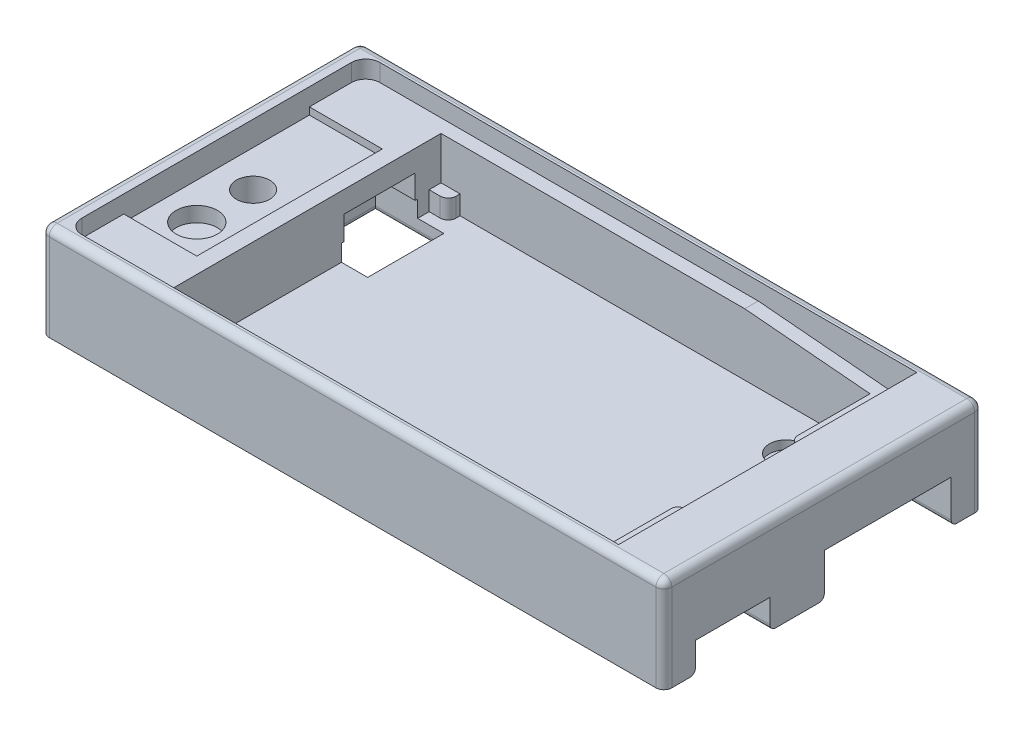
SolidWorks part; units mm, degrees
ref_plane "前视基准面" through (0, 0, 0) normal (0, 0, 1) x (1, 0, 0)
ref_plane "上视基准面" through (0, 0, 0) normal (0, 1, 0) x (1, 0, 0)
ref_plane "右视基准面" through (0, 0, 0) normal (1, 0, 0) x (0, 0, -1)
other "Configuration Table"
sketch "草图1" plane through (0, 0, 0) normal (0, 1, 0) x (1, 0, 0)
  line L0 (-39.25, 0) -> (39.25, 0) construction
  line L1 (-39.25, 20.1) -> (39.25, 20.1)
  line L2 (-39.25, 20.1) -> (-39.25, -20.1)
  line L3 (-39.25, -20.1) -> (39.25, -20.1)
  line L4 (39.25, 20.1) -> (39.25, -20.1)
  line L5 (-39.25, 20.1) -> (39.25, -20.1) construction
  line L6 (-39.25, -20.1) -> (39.25, 20.1) construction
  line L7 (-26.05, -17.1) -> (28.05, -17.1)
  line L8 (-26.05, -17.1) -> (-26.05, 17.1)
  line L9 (-26.05, 17.1) -> (28.05, 17.1)
  line L10 (28.05, -17.1) -> (28.05, 17.1)
  line L12 (32.25, 6.9973) -> (34.45, 6.9973)
  line L13 (32.25, 6.9973) -> (32.25, -6.9973)
  line L14 (32.25, -6.9973) -> (34.45, -6.9973)
  line L15 (34.45, 6.9973) -> (34.45, -6.9973)
  line L16 (-37.25, 18.8) -> (32.25, 18.8)
  line L17 (-37.25, 18.8) -> (-37.25, -18.8)
  line L18 (-37.25, -18.8) -> (32.25, -18.8)
  line L19 (32.25, 18.8) -> (32.25, -18.8)
  circle A0 centre (-32.65, 7.1) radius 2.6
  circle A1 centre (-32.65, 0) radius 2.1
  circle A2 centre (22.85, 11.6973) radius 2.1
  circle A3 centre (22.85, -11.6973) radius 2.1
  circle A4 centre (-32.65, -7.1) radius 2.6
  point P0 (0, 0)
  dimension "D1" = 4.2
  dimension "D6" = 5.2
  dimension "D2" = 5.2
  dimension "D3" = 5.4027
  dimension "D4" = 6.6
  dimension "D5" = 13
  dimension "D7" = 3
  dimension "D8" = 3
  dimension "D9" = 6.6
  dimension "D10" = 11.2
  dimension "D11" = 54.1
  dimension "D12" = 34.2
  dimension "D13" = 2.2
  dimension "D14" = 4.7
  dimension "D15" = 1.3
  dimension "D16" = 1.3
  dimension "D17" = 2
  dimension "D18" = 7
extrude "凸台-拉伸2" add sketch "草图1" along normal blind 2.2 contours L4 L1 L2 L3 L16 L19 L10 L12 L15 L14 L18 L17 | L15 L12 L10 L14 region at (0, 0, -19.2181) region at (33.35, 0, 0)
extrude "凸台-拉伸3" add sketch "草图1<4>" against normal blind 7.8 contours L19 L16 L17 L18 L7 L8 L9 A0 A1 A4 | L4 L1 L2 L3 L16 L19 L10 L12 L15 L14 L18 L17 | A4 | A0 | A1 | L15 L12 L13 L14 region at (0, 0, -19.2181) region at (33.35, 0, 0) region at (31.4598, 0, 0) region at (-32.65, 0, -7.1) region at (-32.65, 0, 0) region at (-32.65, 0, 7.1)
sketch "草图1<4>" plane through (0, 0, 0) normal (0, 1, 0) x (1, 0, 0) same geometry as "草图1"
sketch "草图2" plane through (0, 0, 0) normal (0, 1, 0) x (1, 0, 0)
  line L0 (-37.25, 18.8) -> (-37.25, -18.8) construction
  line L1 (-37.25, 11.7) -> (-28.05, 11.7)
  line L2 (-37.25, 11.7) -> (-37.25, -11.7)
  line L3 (-37.25, -11.7) -> (-28.05, -11.7)
  line L4 (-28.05, 11.7) -> (-28.05, -11.7)
  circle A0 centre (-32.65, 7.1) radius 2.6 construction
  circle A1 centre (-32.65, 7.1) radius 2.6 construction
  circle A2 centre (-32.65, -7.1) radius 2.6 construction
  circle A3 centre (-32.65, -7.1) radius 2.6 construction
  dimension "D1" = 4.6
  dimension "D2" = 4.6
  dimension "D3" = 4.6
extrude "切除-拉伸1" cut sketch "草图2" against normal blind 0.9
sketch "草图6" plane through (0, -0.9, 0) normal (0, 1, 0) x (1, 0, 0)
  circle A0 centre (-32.65, 7.1) radius 2.6 construction
  circle A1 centre (-32.65, 7.1) radius 2.6
  circle A2 centre (-32.65, -7.1) radius 2.6 construction
  circle A3 centre (-32.65, -7.1) radius 2.6
extrude "切除-拉伸2" cut sketch "草图6" against normal blind 1.9 contours A3 region at (-32.65, -0.9, 7.1)
sketch "草图7" plane through (0, -0.9, 0) normal (0, 1, 0) x (1, 0, 0)
  circle A0 centre (-32.65, 0) radius 2.1 construction
  circle A1 centre (-32.65, 0) radius 2.1
extrude "切除-拉伸3" cut sketch "草图7" against normal blind 1.1
sketch "草图8" plane through (0, -2, 0) normal (0, 1, 0) x (1, 0, 0)
  circle A0 centre (-32.65, 0) radius 1.2
  dimension "2.2" = 2.4
extrude "切除-拉伸4" cut sketch "草图8" against normal through all
sketch "草图9" plane through (0, -7.8, 0) normal (0, -1, 0) x (1, 0, 0)
  line L0 (39.25, -20.1) -> (39.25, 20.1) construction
  line L1 (-39.25, -20.1) -> (39.25, -20.1) construction
  line L2 (-39.25, -20.1) -> (-39.25, 20.1) construction
  line L3 (-39.25, 20.1) -> (39.25, 20.1) construction
  line L4 (39.25, -20.1) -> (39.25, 20.1)
  line L5 (-39.25, -20.1) -> (39.25, -20.1)
  line L6 (-39.25, -20.1) -> (-39.25, 20.1)
  line L7 (-39.25, 20.1) -> (39.25, 20.1)
extrude "凸台-拉伸4" add sketch "草图9" along normal blind 2
sketch "草图10" plane through (0, -7.8, 0) normal (0, 1, 0) x (1, 0, 0)
  circle A0 centre (22.85, -11.6973) radius 2.1 construction
  circle A1 centre (22.85, 11.6973) radius 2.1 construction
  circle A2 centre (22.85, -11.6973) radius 2.1
  circle A3 centre (22.85, 11.6973) radius 2.1
extrude "切除-拉伸5" cut sketch "草图10" against normal blind 1.1
sketch "草图11" plane through (0, -8.9, 0) normal (0, 1, 0) x (1, 0, 0)
  circle A0 centre (22.85, 11.6973) radius 1.2
  circle A1 centre (22.85, -11.6973) radius 1.2
  dimension "D1" = 2.4
  dimension "D2" = 2.4
extrude "切除-拉伸6" cut sketch "草图11" against normal through all
sketch "草图12" plane through (0, -9.8, 0) normal (0, -1, 0) x (1, 0, 0)
  line L0 (-26.05, -17.1) -> (28.05, -17.1) construction
  line L1 (-26.05, -17.1) -> (28.05, -17.1) construction
  line L7 (-30.8239, -4.85) -> (-26.3739, -4.85)
  line L8 (-30.8239, -4.85) -> (-30.8239, -13.85)
  line L9 (-30.8239, -13.85) -> (-26.3739, -13.85)
  line L10 (-26.3739, -4.85) -> (-26.3739, -13.85)
  line L11 (-30.8239, -4.85) -> (-26.3739, -13.85) construction
  line L12 (-30.8239, -13.85) -> (-26.3739, -4.85) construction
  line L13 (-28.5989, -9.35) -> (-23.0895, -9.35) construction
  line L14 (-31.3739, -4.55) -> (-26.3739, -4.55)
  line L15 (-31.3739, -4.55) -> (-31.3739, -14.15)
  line L16 (-31.3739, -14.15) -> (-26.3739, -14.15)
  line L17 (-26.3739, -4.55) -> (-26.3739, -14.15)
  point P6 (-28.5989, -9.35)
  dimension "D1" = 7.75
  dimension "D2" = 4.45
  dimension "D3" = 9
  dimension "D4" = 9.6
  dimension "D5" = 5
extrude "切除-拉伸7" cut sketch "草图12" against normal blind 7.1 contours L10 L7 L8 L9 region at (-28.5989, -9.8, -9.35)
extrude "切除-拉伸8" cut sketch "草图12<3>" against normal offset from surface (4.1 mm away) 3 contours L17 L14 L15 L16 L9 L8 L7 region at (-30.9321, -9.8, -9.35) up to face at (-28.5989, -2.7, -9.35)
sketch "草图12<3>" plane through (0, -9.8, 0) normal (0, -1, 0) x (1, 0, 0) same geometry as "草图12"
sketch "草图13" plane through (-26.3739, 0, 0) normal (-1, 0, 0) x (0, 0, 1)
  line L4 (-4.85, -2.7) -> (-13.85, -2.7)
  line L5 (-4.85, -2.7) -> (-13.85, -2.7)
  line L9 (-13.85, -2.7) -> (-13.85, -5.7)
  line L11 (-13.85, -5.7) -> (-14.15, -5.7)
  line L12 (-14.15, -9.8) -> (-4.55, -9.8)
  line L13 (-13.85, -5.7) -> (-14.15, -5.7)
  line L14 (-14.15, -5.7) -> (-14.15, -9.8)
  line L15 (-4.85, -5.7) -> (-4.85, -2.7)
  line L17 (-13.85, -2.7) -> (-13.85, -5.7)
  line L20 (-14.15, -9.8) -> (-4.55, -9.8)
  line L23 (-4.85, -5.7) -> (-4.85, -2.7)
  line L24 (-14.15, -5.7) -> (-14.15, -9.8)
  line L25 (-4.55, -9.8) -> (-4.55, -5.7)
  line L26 (-4.55, -9.8) -> (-4.55, -5.7)
  line L27 (-4.55, -5.7) -> (-4.85, -5.7)
  line L28 (-4.55, -5.7) -> (-4.85, -5.7)
  dimension "D1" = 0
extrude "切除-拉伸9" cut sketch "草图13" against normal up to surface (0.3239 mm away) up to face at (-26.05, -3.9, 0)
sketch "草图14" plane through (-26.05, 0, 0) normal (-1, 0, 0) x (0, 0, 1)
  line L4 (-14.15, -7.8) -> (-14.15, -9.8)
  line L5 (-14.15, -9.8) -> (-4.55, -9.8)
  line L7 (-4.55, -7.8) -> (-14.15, -7.8)
  line L9 (-14.15, -9.8) -> (-4.55, -9.8)
  line L11 (-4.55, -7.8) -> (-14.15, -7.8)
  line L12 (-14.15, -7.8) -> (-14.15, -9.8)
  line L14 (-4.55, -9.8) -> (-4.55, -7.8)
  line L15 (-4.55, -9.8) -> (-4.55, -7.8)
  dimension "D1" = 0
extrude "切除-拉伸10" cut sketch "草图14" against normal blind 3.3
fillet "圆角1" radius 1.8 4 edges at (32.25, 1.1, 18.8) (32.25, 1.1, -18.8) (-37.25, 1.1, -18.8) (-37.25, 1.1, 18.8)
fillet "圆角2" radius 1 8 edges at (39.25, -3.8, -20.1) (39.25, 2.2, 0) (39.25, -3.8, 20.1) (0, 2.2, -20.1) (-39.25, -3.8, -20.1) (0, 2.2, 20.1) (-39.25, 2.2, 0) (-39.25, -3.8, 20.1)
sketch "草图15" plane through (0, -7.8, 0) normal (0, 1, 0) x (1, 0, 0)
  line L0 (0, 0) -> (25.0264, 0) construction
  line L1 (-26.05, 17.1) -> (-23.65, 17.1)
  line L2 (-26.05, 17.1) -> (-26.05, 15.6)
  line L3 (-26.05, 15.6) -> (-23.65, 15.6)
  line L4 (-23.65, 17.1) -> (-23.65, 15.6)
  line L5 (-26.05, -15.6) -> (-23.65, -15.6)
  line L6 (-23.65, -17.1) -> (-23.65, -15.6)
  line L7 (-26.05, -17.1) -> (-23.65, -17.1)
  line L8 (-26.05, -17.1) -> (-26.05, -15.6)
  dimension "D1" = 2.4
  dimension "D2" = 1.5
extrude "凸台-拉伸5" add sketch "草图15" along normal blind 2.4
sketch "草图16" plane through (0, 0, 0) normal (0, 1, 0) x (1, 0, 0)
  line L0 (0, 0) -> (31.9375, 0) construction
  line L1 (28.05, -17.1) -> (28.05, 17.1) construction
  line L3 (30.2966, 8) -> (30.2966, -8)
  line L4 (32.25, 17) -> (32.25, -17) construction
  line L6 (30.2966, 10.6705) -> (30.2966, 8)
  line L7 (30.2966, -10.6705) -> (30.2966, -8)
  arc A0 (29.9431, 7.24) -> (30.2966, 10.6705) centre (31.4789, 8.8152) cw
  arc A1 (29.9431, -7.24) -> (30.2966, -10.6705) centre (31.4789, -8.8152) ccw
  ellipse E0 centre (28.05, 0) end of major axis (28.05, -8.1106) minor radius 4.2 (29.9431, -7.24) -> (29.9431, 7.24) ccw
  dimension "D1" = 2.2
revolve "切除-旋转1" [suppressed] cut sketch "草图16" angle 360 about L3
sketch "草图17" plane through (0, -7.8, 0) normal (0, 1, 0) x (1, 0, 0)
  circle A1 centre (-32.65, 0) radius 1.2
  circle A2 centre (-32.65, 0) radius 1.2
  dimension "D1" = 0
extrude "切除-拉伸11" cut sketch "草图17" against normal through all
sketch "草图19" plane through (0, 0, 20.1) normal (0, 0, 1) x (1, 0, 0)
  line L0 (12.25, 0) -> (34.1406, 0.2) construction
  line L1 (32.25, 2.2) -> (30.45, 2.2) construction
  line L2 (12.25, 0) -> (32.25, 2) construction
  line L6 (12.25, 0) -> (12.25, 2)
  line L11 (12.25, 0) -> (34.05, -2) construction
  line L12 (12.25, 0) -> (32.2733, -1.7518)
  line L13 (12.25, 0) -> (33.7215, -4.2678) construction
  line L14 (32.25, 2) -> (32.25, 0) construction
  line L15 (32.25, 0) -> (30.25, 0) construction
  line L17 (12.25, 2) -> (12.25, 3)
  line L18 (12.25, 3) -> (32.25, 3)
  line L19 (32.25, 2) -> (32.25, 3)
  line L20 (32.25, 2.2) -> (30.45, 2.2) construction
  line L21 (-35.45, 0) -> (30.45, 0) construction
  line L22 (-35.45, 0) -> (30.25, 0) construction
  line L23 (12.25, 2) -> (32.25, 2) construction
  line L24 (34.1416, 0) -> (32.3498, 0) construction
  line L25 (30.25, 0) -> (34.05, 0) construction
  line L26 (30.25, 0) -> (30.25, -2) construction
  line L27 (30.25, -2) -> (34.05, -2) construction
  line L28 (34.05, 0) -> (34.05, -2) construction
  line L29 (33.7215, -4.2678) -> (25.7215, -2.6777)
  line L30 (25.7215, -2.6777) -> (25.8517, -1.19)
  line L31 (34.1406, 0.2) -> (32.3489, 0.1836)
  circle A0 centre (12.25, 0) radius 20.0998 construction
  arc A3 (32.25, 2) -> (32.2733, -1.7518) centre (12.25, 0) cw
  circle A4 centre (12.25, 0) radius 21.8916 construction
  arc A5 (33.7215, -4.2678) -> (34.1406, 0.2) centre (12.25, 0) ccw
  line M8 (38.25, 1.2) -> (-38.25, 1.2)
  dimension "D1" = 2
  dimension "D2" = 20
  dimension "D3" = 5
  dimension "D4" = 2
  dimension "D5" = 20
  dimension "D6" = 6
  dimension "D7" = 1
  dimension "D8" = 1.8
  dimension "D9" = 2
  dimension "D10" = 8
  dimension "D11" = 0.2
extrude "切除-拉伸12" cut sketch "草图19" against normal up to surface (38.9 mm away) from surface contours L6 L12 M8 | L6 M8 region at (23.7042, 0.0997, 20.1) region at (22.2577, 2.0995, 20.1) up to face at (-2.5, 1.1, -18.8) starting at face at (-2.5, 1.1, 18.8)
extrude "切除-拉伸13" cut sketch "草图19<3>" against normal up to vertex (27.0973 mm away) from vertex contours L27 L12 L13 region at (30.7321, -2.2329, 20.1) up to point (34.45, 0, -6.9973) starting at point (34.45, 0, 6.9973)
sketch "草图19<3>" plane through (0, 0, 20.1) normal (0, 0, 1) x (1, 0, 0) same geometry as "草图19"
sketch "草图20" plane through (0.3556, 2.3642, 0) normal (0.195, 0.9808, 0) x (0.9808, -0.195, 0)
  line L0 (0.1121, 0) -> (28.2361, 0) construction
  line L1 (28.2361, 6.9973) -> (28.2361, -6.9973) construction
  line L2 (28.2361, 6.9973) -> (28.2361, -6.9973) construction
  line L3 (28.2361, 5.3609) -> (28.2361, -5.3609)
  line L4 (28.2361, 0) -> (31.3144, 0) construction
  line L5 (31.3144, 18.8) -> (31.3144, -18.8) construction
  line L6 (29.3869, 4.2263) -> (28.2361, 5.3609) construction
  line L9 (28.2361, -5.3609) -> (28.2361, 5.3609) construction
  ellipse E0 centre (28.2361, 0) end of major axis (28.2361, 5.3609) minor radius 3.0783 (28.2361, 5.3609) -> (28.2361, -5.3609) cw
revolve "切除-旋转2" [suppressed] cut sketch "草图20" angle 360 about L3
fillet "圆角4" [suppressed] radius 1
fillet "圆角5" radius 1 2 edges at (-23.65, -6.6, 15.6) (-23.65, -6.6, -15.6)
sketch "草图21" plane through (0, -2, 0) normal (0, 1, 0) x (1, 0, 0)
  circle A1 centre (-32.65, 0) radius 2.1
  circle A2 centre (-32.65, 0) radius 2.1
  dimension "D1" = 0
extrude "切除-拉伸14" cut sketch "草图21" against normal up to surface (6.9 mm away) up to face at (22.85, -8.9, -10.4973)
sketch "草图22" plane through (0, -9.8, 0) normal (0, -1, 0) x (1, 0, 0)
  line L0 (0, 0) -> (39.25, 0) construction
  line L2 (-39.25, 14.6675) -> (-39.25, 5.2675)
  line L3 (31.35, 16.1208) -> (39.25, 16.1208)
  line L4 (31.35, 16.1208) -> (31.35, 6.7208)
  line L5 (31.35, 6.7208) -> (39.25, 6.7208)
  line L6 (39.25, 16.1208) -> (39.25, 6.7208)
  line L7 (31.35, 16.1208) -> (39.25, 6.7208) construction
  line L8 (31.35, 6.7208) -> (39.25, 16.1208) construction
  line L9 (-39.25, 14.6675) -> (-31.35, 14.6675)
  line L10 (-39.25, 5.2675) -> (-31.35, 5.2675)
  line L11 (-31.35, 14.6675) -> (-31.35, 5.2675)
  line L13 (39.25, -19.1) -> (39.25, 19.1) construction
  line L14 (-39.25, 19.1) -> (-39.25, -19.1) construction
  point P5 (35.3, 11.4208)
  dimension "D1" = 7.9
  dimension "D2" = 9.4
extrude "切除-拉伸15" cut sketch "草图22" against normal blind 3.7
sketch "草图23" plane through (0, -9.8, 0) normal (0, -1, 0) x (1, 0, 0)
  line L1 (39.25, -16.1357) -> (30.85, -16.1357)
  line L2 (39.25, -16.1357) -> (39.25, -0.1357)
  line L3 (39.25, -0.1357) -> (30.85, -0.1357)
  line L4 (30.85, -16.1357) -> (30.85, -0.1357)
  line L6 (32.2733, -18.8) -> (12.25, -18.8) construction
  line L7 (32.2733, -18.8) -> (12.25, -18.8) construction
  line L8 (39.25, -19.1) -> (39.25, 6.7208) construction
  line L9 (39.25, -19.1) -> (39.25, 6.7208) construction
  dimension "D1" = 8.4
  dimension "D2" = 16
extrude "切除-拉伸16" cut sketch "草图23" against normal blind 5.4
fillet "圆角6" radius 0.7 13 edges at (-35.3, -9.8, 5.2675) (35.05, -9.8, -16.1357) (30.85, -9.8, -8.1357) (35.05, -9.8, -0.1357) (35.3, -9.8, 6.7208) (35.3, -9.8, 16.1208) (31.35, -9.8, 11.4208) (-22.75, -9.8, -9.35) (-27.0619, -9.8, -14.15) (-31.3739, -9.8, -9.35) (-27.0619, -9.8, -4.55) (-31.35, -9.8, 9.9675) (-35.3, -9.8, 14.6675)
fillet "圆角7" radius 1 3 edges at (28.05, -2.2614, 6.9973) (28.05, -2.2614, -6.9973) (28.05, -3.1405, 0)
